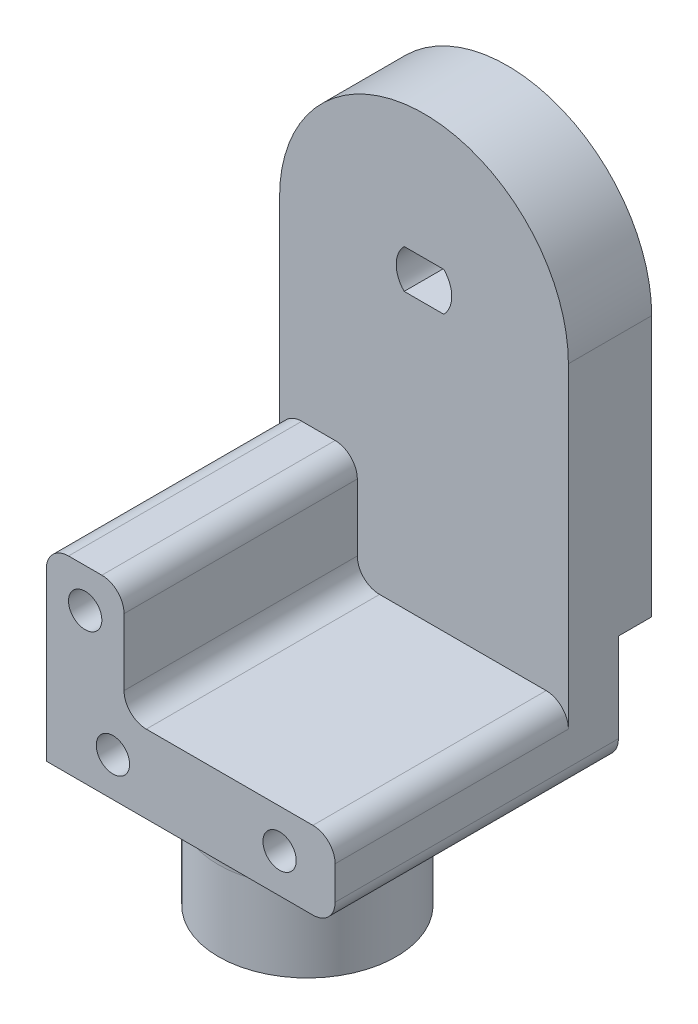
SolidWorks part; units mm, degrees
ref_plane "Front Plane" through (0, 0, 0) normal (0, 0, 1) x (1, 0, 0)
ref_plane "Top Plane" through (0, 0, 0) normal (0, 1, 0) x (1, 0, 0)
ref_plane "Right Plane" through (0, 0, 0) normal (1, 0, 0) x (0, 0, -1)
sketch "Sketch1" plane through (0, 0, 0) normal (0, 0, 1) x (1, 0, 0)
  line L7 (24.2641, -54) -> (50.2641, -54)
  line L9 (24.2641, -4) -> (50.2641, -4)
  line L10 (24.2641, -54) -> (24.2641, -4)
  line L11 (50.2641, -54) -> (50.2641, -4)
  line L14 (39.0495, -22.266) -> (35.4787, -22.266)
  line L15 (35.4787, -18.766) -> (39.0495, -18.766)
  line L16 (37.2641, -4) -> (37.2641, -54) construction
  arc A5 (35.4787, -18.766) -> (35.4787, -22.266) centre (37.2641, -20.516) ccw
  arc A6 (39.0495, -22.266) -> (39.0495, -18.766) centre (37.2641, -20.516) ccw
extrude "Boss-Extrude1" add sketch "Sketch1" along normal blind 8
sketch "Sketch2" plane through (0, 0, -20) normal (0, 0, -1) x (-1, 0, 0)
  line L0 (-39.0495, -18.766) -> (-35.4787, -18.766) construction
  line L1 (-35.4787, -22.266) -> (-39.0495, -22.266) construction
  line L2 (-39.0495, -18.766) -> (-35.4787, -18.766)
  line L3 (-35.4787, -22.266) -> (-39.0495, -22.266)
  line L4 (-50.2641, -4) -> (-50.2641, -54)
  line L5 (-24.2641, -4) -> (-50.2641, -4)
  line L6 (-24.2641, -4) -> (-50.2641, -4)
  line L7 (-50.2641, -4) -> (-50.2641, -54)
  line L9 (-50.2641, -54) -> (-24.2641, -54)
  line L10 (-24.2641, -54) -> (-24.2641, -4)
  line L16 (-50.2641, -54) -> (-24.2641, -54)
  line L17 (-24.2641, -54) -> (-24.2641, -4)
  arc A0 (-39.0495, -18.766) -> (-39.0495, -22.266) centre (-37.2641, -20.516) ccw construction
  arc A1 (-35.4787, -22.266) -> (-35.4787, -18.766) centre (-37.2641, -20.516) ccw construction
  arc A2 (-39.0495, -18.766) -> (-39.0495, -22.266) centre (-37.2641, -20.516) ccw
  arc A3 (-35.4787, -22.266) -> (-35.4787, -18.766) centre (-37.2641, -20.516) ccw
  dimension "D1" = 0
extrude "Boss-Extrude2" add sketch "Sketch2" along normal blind 8 separate body
sketch "Sketch3" plane through (0, 0, 8) normal (0, 0, 1) x (1, 0, 0)
  line L0 (24.2641, -54) -> (50.2641, -54) construction
  line L2 (24.2641, -54) -> (50.2641, -54)
  line L4 (24.2641, -47) -> (50.2641, -47)
  line L6 (50.2641, -47) -> (64.2641, -47) construction
  line L8 (24.2641, -54) -> (24.2641, -47)
  line L10 (50.2641, -54) -> (64.2641, -54) construction
  line L11 (50.2641, -54) -> (50.2641, -4) construction
  line L12 (50.2641, -54) -> (50.2641, -47)
  dimension "D1" = 7
extrude "Boss-Extrude3" add sketch "Sketch3" against normal up to surface (36 mm away) up to face at (37.2641, -29, -28)
sketch "Sketch4" plane through (0, -54, 0) normal (0, -1, 0) x (1, 0, 0)
  line L0 (24.2641, 8) -> (50.2641, 8) construction
  line L1 (37.2641, 8) -> (37.2641, -28) construction
  line L2 (24.2641, -28) -> (50.2641, -28) construction
  line L3 (37.2641, -10) -> (43.8453, -10) construction
  circle A0 centre (37.2641, -10) radius 8
  circle A1 centre (37.2641, -10) radius 5
extrude "Boss-Extrude4" add sketch "Sketch4" along normal blind 10
fillet "Fillet2" radius 3 2 edges at (24.2641, -29, 8) (24.2641, -29, -28)
sketch "Sketch6" plane through (0, 0, -20) normal (0, 0, 1) x (1, 0, 0)
  line L0 (27.2641, -54) -> (50.2641, -54) construction
  line L1 (24.2641, -37) -> (31.2641, -37)
  line L2 (24.2641, -37) -> (24.2641, -54)
  line L3 (24.2641, -54) -> (31.2641, -54)
  line L4 (31.2641, -37) -> (31.2641, -54)
extrude "Boss-Extrude5" add sketch "Sketch6" along normal up to surface (20 mm away) up to face at (37.2641, -25.5, 0)
chamfer "Chamfer1" distance 2 angle 45 1 edges at (37.2641, -54, -2)
sketch "Sketch7" plane through (0, 0, 0) normal (0, 0, -1) x (-1, 0, 0)
  line L6 (-50.2641, -4) -> (-50.2641, -47)
  line L7 (-50.2641, -4) -> (-50.2641, -47)
  line L8 (-50.2641, -47) -> (-31.2641, -47)
  line L9 (-31.2641, -47) -> (-31.2641, -37)
  line L10 (-31.2641, -37) -> (-24.2641, -37)
  line L11 (-31.2641, -37) -> (-24.2641, -37)
  line L12 (-24.2641, -37) -> (-24.2641, -4)
  line L15 (-50.2641, -47) -> (-31.2641, -47)
  line L16 (-31.2641, -47) -> (-31.2641, -37)
  line L21 (-24.2641, -37) -> (-24.2641, -4)
  line L22 (-24.2641, -4) -> (-50.2641, -4)
  line L23 (-24.2641, -4) -> (-50.2641, -4)
  dimension "D1" = 0
extrude "Cut-Extrude2" cut sketch "Sketch7" against normal blind 0.5
sketch "Sketch8" plane through (0, 0, -20) normal (0, 0, 1) x (1, 0, 0)
  line L6 (50.2641, -47) -> (50.2641, -4)
  line L7 (31.2641, -47) -> (50.2641, -47)
  line L8 (50.2641, -47) -> (50.2641, -4)
  line L10 (50.2641, -4) -> (24.2641, -4)
  line L11 (50.2641, -4) -> (24.2641, -4)
  line L12 (24.2641, -4) -> (24.2641, -37)
  line L13 (31.2641, -37) -> (31.2641, -47)
  line L14 (31.2641, -47) -> (50.2641, -47)
  line L20 (31.2641, -37) -> (31.2641, -47)
  line L21 (24.2641, -4) -> (24.2641, -37)
  line L22 (24.2641, -37) -> (31.2641, -37)
  line L23 (24.2641, -37) -> (31.2641, -37)
  dimension "D1" = 0
extrude "Cut-Extrude3" cut sketch "Sketch8" against normal blind 0.5
sketch "Sketch10" plane through (0, 0, 8) normal (0, 0, 1) x (1, 0, 0)
  line L0 (50.2641, -20.516) -> (50.2641, 2.2658)
  line L1 (50.2641, 2.2658) -> (24.2641, 2.2658)
  line L2 (24.2641, 2.2658) -> (24.2641, -20.516)
  arc A0 (50.2641, -20.516) -> (24.2641, -20.516) centre (37.2641, -20.516) ccw
extrude "Cut-Extrude4" cut sketch "Sketch10" against normal up to surface (36 mm away) up to face at (38.7641, -29, -28)
sketch "Sketch11" plane through (0, 0, 8) normal (0, 0, 1) x (1, 0, 0)
  line L0 (24.2641, -54) -> (24.2641, -20.516) construction
  line L1 (50.2641, -54) -> (24.2641, -54)
  line L2 (50.2641, -54) -> (50.2641, -44)
  line L3 (50.2641, -44) -> (24.2641, -44)
  line L4 (24.2641, -54) -> (24.2641, -44)
extrude "Cut-Extrude5" cut sketch "Sketch11" against normal blind 3
sketch "Sketch12" plane through (0, 0, -28) normal (0, 0, -1) x (-1, 0, 0)
  line L4 (-50.2641, -44) -> (-50.2641, -54)
  line L5 (-24.2641, -44) -> (-50.2641, -44)
  line L6 (-24.2641, -54) -> (-24.2641, -44)
  line L7 (-50.2641, -54) -> (-24.2641, -54)
  line L8 (-50.2641, -44) -> (-50.2641, -54)
  line L9 (-24.2641, -44) -> (-50.2641, -44)
  line L10 (-24.2641, -54) -> (-24.2641, -44)
  line L11 (-50.2641, -54) -> (-24.2641, -54)
  dimension "D1" = 0
extrude "Cut-Extrude6" cut sketch "Sketch12" against normal blind 3
sketch "Sketch13" plane through (0, 0, 8) normal (0, 0, 1) x (1, 0, 0)
  line L0 (31.2641, -37) -> (31.2641, -47) construction
  line L1 (31.2641, -37) -> (31.2641, -47) construction
  line L2 (31.2641, -37) -> (24.2641, -37) construction
  circle A0 centre (45.2641, -50.5) radius 1.5
  circle A1 centre (30.2641, -50.5) radius 1.5
  circle A2 centre (27.7641, -40.5) radius 1.5
extrude "Cut-Extrude7" cut sketch "Sketch13" against normal up to surface (36 mm away) up to face at (39.4931, -28.1629, -28)
sketch "Sketch14" plane through (0, 0, 8) normal (0, 0, 1) x (1, 0, 0)
  line L1 (52.1631, -6.1028) -> (22.4004, -6.1028)
  line L2 (52.1631, -6.1028) -> (52.1631, -65.4423)
  line L3 (52.1631, -65.4423) -> (22.4004, -65.4423)
  line L4 (22.4004, -6.1028) -> (22.4004, -65.4423)
extrude "Cut-Extrude8" cut sketch "Sketch14" against normal up to surface (7.5 mm away) up to face at (37.2641, -20.516, 0.5)
sketch "Sketch15" plane through (0, 0, -28) normal (0, 0, -1) x (-1, 0, 0)
  circle A0 centre (-27.7641, -40.5) radius 2.25
extrude "Cut-Extrude9" cut sketch "Sketch15" against normal blind 6
fillet "Fillet3" radius 2 5 edges at (50.2641, -47, -10) (31.2641, -47, -10) (31.2641, -37, -10) (24.2641, -37, -10) (50.2641, -54, -12.25)
fillet "Fillet4" radius 2 2 edges at (37.2641, -56, -2) (37.2641, -54, 0)
